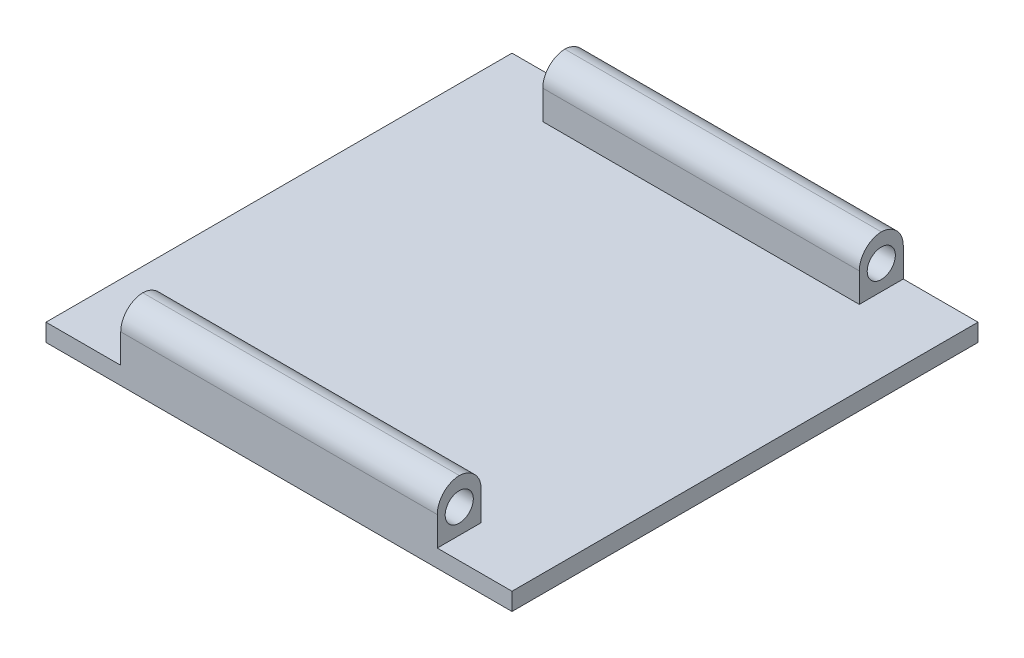
SolidWorks part; units mm, degrees
ref_plane "Front Plane" through (0, 0, 0) normal (0, 0, 1) x (1, 0, 0)
ref_plane "Top Plane" through (0, 0, 0) normal (0, 1, 0) x (1, 0, 0)
ref_plane "Right Plane" through (0, 0, 0) normal (1, 0, 0) x (0, 0, -1)
sketch "Sketch1" plane through (0, 0, 0) normal (0, 1, 0) x (1, 0, 0)
  line L1 (-26.5, -26.5) -> (26.5, -26.5)
  line L2 (-26.5, -26.5) -> (-26.5, 26.5)
  line L3 (-26.5, 26.5) -> (26.5, 26.5)
  line L4 (26.5, -26.5) -> (26.5, 26.5)
  line L5 (-26.5, -26.5) -> (26.5, 26.5) construction
  line L6 (-26.5, 26.5) -> (26.5, -26.5) construction
  point P0 (0, 0)
  dimension "D1" = 53
  dimension "D2" = 53
extrude "Boss-Extrude1" add sketch "Sketch1" along normal blind 2
sketch "Sketch2" plane through (0, 2, 0) normal (0, 1, 0) x (1, 0, 0)
  line L0 (0, 26.5) -> (0, -26.5) construction
  line L1 (26.5, 26.5) -> (-26.5, 26.5) construction
  line L2 (-18, 26.5) -> (18, 26.5)
  line L3 (-18, 26.5) -> (-18, 21.5)
  line L4 (-18, 21.5) -> (18, 21.5)
  line L5 (18, 21.5) -> (18, 26.5)
  line L6 (-39.9594, 0) -> (39.9594, 0) construction
  line L7 (-18, -21.5) -> (18, -21.5)
  line L8 (-18, -26.5) -> (-18, -21.5)
  line L9 (-18, -26.5) -> (18, -26.5)
  line L10 (18, -21.5) -> (18, -26.5)
  point P2 (0, 0)
  point P3 (0, 26.5)
  point P9 (-14, 22)
  dimension "D1" = 36
  dimension "D2" = 5
extrude "Boss-Extrude2" add sketch "Sketch2" along normal blind 5.9
sketch "Sketch3" plane through (18, 0, 0) normal (1, 0, 0) x (0, 0, -1)
  line L0 (-26.5, 7.9) -> (-21.5, 7.9) construction
  line L1 (-21.5, 7.9) -> (-21.5, 2) construction
  line L2 (-21.5, 2) -> (-26.5, 2) construction
  line L3 (-26.5, 2) -> (-26.5, 7.9) construction
  line L4 (-24, 7.9) -> (-24, 2) construction
  line L5 (0, 39.9594) -> (0, -39.9594) construction
  circle A0 centre (-24, 4.8) radius 1.6
  circle A1 centre (24, 4.8) radius 1.6
  point P12 (-24, 5)
  dimension "D1" = 3.2
  dimension "D2" = 2.8
extrude "Cut-Extrude1" cut sketch "Sketch3" against normal blind 3.6
sketch "Sketch4" plane through (-18, 0, -18) normal (1, 0, 0) x (0, 0, -1)
  line L0 (-44.5, 7.9) -> (-39.5, 7.9) construction
  line L1 (-39.5, 7.9) -> (-39.5, 2) construction
  line L2 (-39.5, 2) -> (-44.5, 2) construction
  line L3 (-44.5, 2) -> (-44.5, 7.9) construction
  line L4 (-42, 7.9) -> (-42, 2) construction
  line L6 (-18, 39.9594) -> (-18, -39.9594) construction
  circle A0 centre (-42, 4.8) radius 1.6
  circle A2 centre (6, 4.8) radius 1.6
  point P12 (-24, 5)
  point P13 (-44.5, 7.9)
  point P14 (-39.5, 7.9)
  point P19 (-39.5, 2)
  dimension "D1" = 3.2
  dimension "D2" = 2.8
extrude "Cut-Extrude2" cut sketch "Sketch4" along normal blind 3.6
fillet "Fillet1" radius 2.6 4 edges at (0, 7.9, -26.5) (0, 7.9, -21.5) (0, 7.9, 21.5) (0, 7.9, 26.5)
